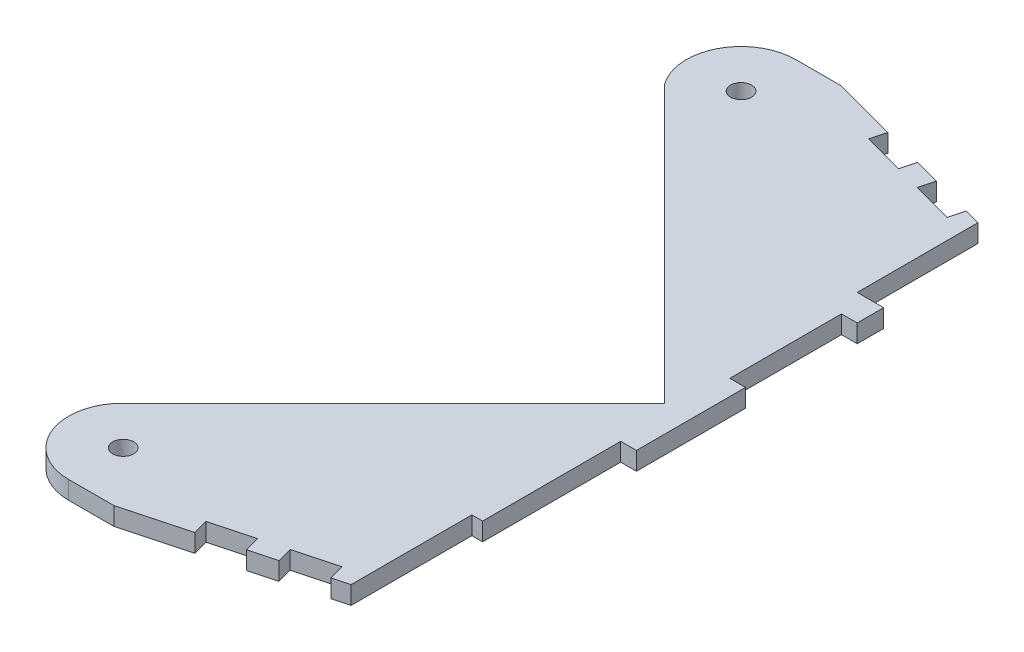
SolidWorks part; units mm, degrees
ref_plane "Front" through (0, 0, 0) normal (0, 0, 1) x (1, 0, 0)
ref_plane "Top" through (0, 0, 0) normal (0, 1, 0) x (1, 0, 0)
ref_plane "Right" through (0, 0, 0) normal (1, 0, 0) x (0, 0, -1)
ref_axis "side-side" through (80.9, 0, 0) along (-1, 0, 0)
ref_axis "up-down" through (0, 50, 0) along (0, -1, 0)
ref_axis "front-back" through (0, 0, -80.9) along (0, 0, 1)
sketch "Sketch1" plane through (0, 0, 0) normal (0, 1, 0) x (1, 0, 0)
  line L1 (0, 0) -> (-83.6295, 83.6295)
  line L3 (0, -94.8336) -> (-56.6019, -110)
  line L4 (-56.6019, 110) -> (0, 94.8336)
  line L5 (-70.3102, 110) -> (-56.6019, 110)
  line L6 (8, 58.293) -> (8, -58.293)
  line L7 (0, 0) -> (58.8362, 0) construction
  line L8 (-70.3102, -110) -> (-56.6019, -110)
  line L10 (0, 0) -> (-83.6295, -83.6295)
  line L12 (0, 94.8336) -> (0, 58.293)
  line L13 (0, 58.293) -> (8, 58.293)
  line L16 (0, -94.8336) -> (0, -58.293)
  line L17 (0, -58.293) -> (8, -58.293)
  circle A0 centre (-70.3102, 93.4511) radius 3.175
  circle A1 centre (-70.3102, -93.4511) radius 3.175
  arc A2 (-83.6295, 83.6295) -> (-70.3102, 110) centre (-70.3102, 93.4511) cw
  arc A3 (-83.6295, -83.6295) -> (-70.3102, -110) centre (-70.3102, -93.4511) ccw
  dimension "D5" = 6.35
  dimension "D1" = 64.6019
  dimension "D2" = 110
  dimension "D3" = 8
  dimension "D4" = 45
  dimension "D6" = 75
  dimension "D7" = 116.586
  dimension "D8" = 8
extrude "Boss-Extrude1" add sketch "Sketch1" along normal blind 5.461
chamfer "Chamfer1" [suppressed] distance 10 distance2 10
sketch "Sketch3" plane through (0, 0, 0) normal (0, 1, 0) x (1, 0, 0)
  line L33 (-4.8296, 96.1276) -> (-17.1928, 99.4404)
  line L34 (-6.0623, 91.5274) -> (-4.8296, 96.1276)
  line L35 (-18.4255, 94.8401) -> (-6.0623, 91.5274)
  line L36 (-17.1928, 99.4404) -> (-18.4255, 94.8401)
  line L37 (-4.8296, 96.1276) -> (-17.1928, 99.4404)
  line L38 (-6.0623, 91.5274) -> (-4.8296, 96.1276)
  line L39 (-18.4255, 94.8401) -> (-6.0623, 91.5274)
  line L40 (-17.1928, 99.4404) -> (-18.4255, 94.8401)
  line L41 (-24.9202, 101.5109) -> (-37.2834, 104.8236)
  line L42 (-26.1529, 96.9107) -> (-24.9202, 101.5109)
  line L43 (-38.5161, 100.2234) -> (-26.1529, 96.9107)
  line L44 (-37.2834, 104.8236) -> (-38.5161, 100.2234)
  line L45 (-24.9202, 101.5109) -> (-37.2834, 104.8236)
  line L46 (-26.1529, 96.9107) -> (-24.9202, 101.5109)
  line L47 (-38.5161, 100.2234) -> (-26.1529, 96.9107)
  line L48 (-37.2834, 104.8236) -> (-38.5161, 100.2234)
  line L49 (8, 50.293) -> (3.2375, 50.293)
  line L50 (8, 16.51) -> (8, 50.293)
  line L51 (3.2375, 16.51) -> (8, 16.51)
  line L52 (3.2375, 50.293) -> (3.2375, 16.51)
  line L53 (8, 50.293) -> (3.2375, 50.293)
  line L54 (8, 16.51) -> (8, 50.293)
  line L55 (3.2375, 16.51) -> (8, 16.51)
  line L56 (3.2375, 50.293) -> (3.2375, 16.51)
  line L57 (-26.1529, -96.9107) -> (-38.5161, -100.2234)
  line L58 (-24.9202, -101.5109) -> (-26.1529, -96.9107)
  line L59 (-37.2834, -104.8236) -> (-24.9202, -101.5109)
  line L60 (-38.5161, -100.2234) -> (-37.2834, -104.8236)
  line L61 (-26.1529, -96.9107) -> (-38.5161, -100.2234)
  line L62 (-24.9202, -101.5109) -> (-26.1529, -96.9107)
  line L63 (-37.2834, -104.8236) -> (-24.9202, -101.5109)
  line L64 (-38.5161, -100.2234) -> (-37.2834, -104.8236)
  line L65 (-6.0623, -91.5274) -> (-18.4255, -94.8401)
  line L66 (-4.8296, -96.1276) -> (-6.0623, -91.5274)
  line L67 (-17.1928, -99.4404) -> (-4.8296, -96.1276)
  line L68 (-18.4255, -94.8401) -> (-17.1928, -99.4404)
  line L69 (-6.0623, -91.5274) -> (-18.4255, -94.8401)
  line L70 (-4.8296, -96.1276) -> (-6.0623, -91.5274)
  line L71 (-17.1928, -99.4404) -> (-4.8296, -96.1276)
  line L72 (-18.4255, -94.8401) -> (-17.1928, -99.4404)
  line L73 (3.2375, -16.51) -> (3.2375, -50.293)
  line L74 (8, -16.51) -> (3.2375, -16.51)
  line L75 (8, -50.293) -> (8, -16.51)
  line L76 (3.2375, -50.293) -> (8, -50.293)
  line L77 (3.2375, -16.51) -> (3.2375, -62.7995)
  line L78 (8, -16.51) -> (3.2375, -16.51)
  line L79 (8, -62.7995) -> (8, -16.51)
  line L80 (3.2375, -62.7995) -> (8, -62.7995)
  dimension "D1" = 0
  dimension "D2" = 0
  dimension "D3" = 0
  dimension "D4" = 0
  dimension "D5" = 0
  dimension "D6" = 0
extrude "Cut-Extrude2" cut sketch "Sketch3" along normal blind 10
